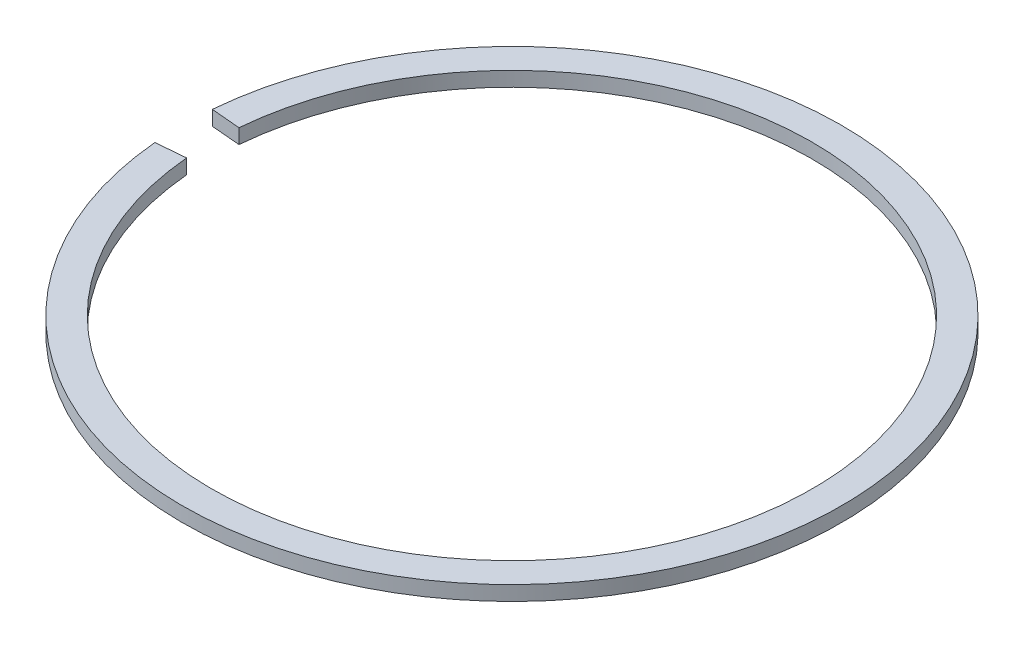
SolidWorks part; units mm, degrees
ref_plane "Front Plane" through (0, 0, 0) normal (0, 0, 1) x (1, 0, 0)
ref_plane "Top Plane" through (0, 0, 0) normal (0, 1, 0) x (1, 0, 0)
ref_plane "Right Plane" through (0, 0, 0) normal (1, 0, 0) x (0, 0, -1)
sketch "Sketch1" plane through (0, 0, 0) normal (0, 0, 1) x (1, 0, 0)
  line L0 (0, 0) -> (0, 6.6804) construction
  line L2 (41, 0.4536) -> (45, 0.4536)
  line L3 (41, 0.4536) -> (41, 2.4536)
  line L4 (41, 2.4536) -> (45, 2.4536)
  line L5 (45, 0.4536) -> (45, 2.4536)
  dimension "D1" = 4
  dimension "D2" = 2
  dimension "D3" = 41
revolve "Revolve1" add sketch "Sketch1" angle 350 mid plane about L0
